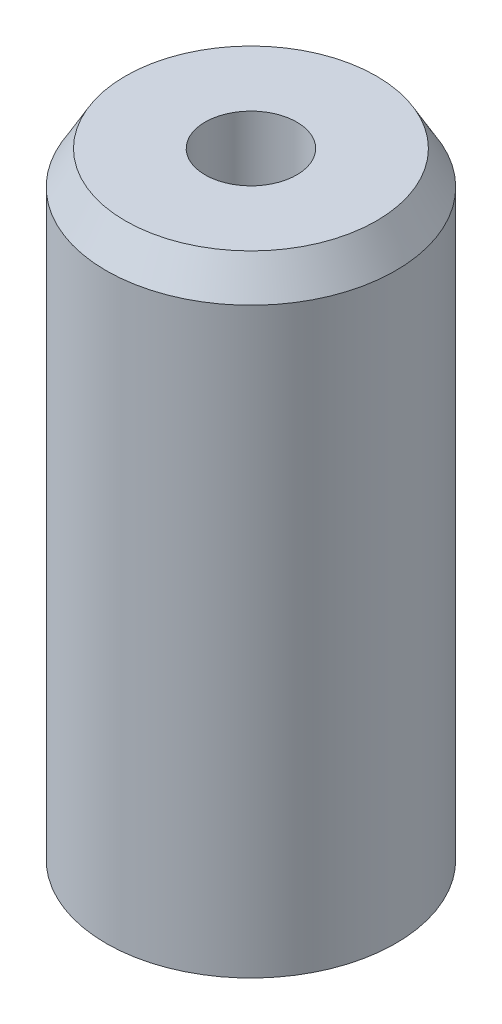
SolidWorks part; units mm, degrees
ref_plane "Front Plane" through (0, 0, 0) normal (0, 0, 1) x (1, 0, 0)
ref_plane "Top Plane" through (0, 0, 0) normal (0, 1, 0) x (1, 0, 0)
ref_plane "Right Plane" through (0, 0, 0) normal (1, 0, 0) x (0, 0, -1)
sketch "Sketch1" plane through (0, 0, 0) normal (0, 1, 0) x (1, 0, 0)
  circle A0 centre (0, 0) radius 20
  dimension "SHAFT_OD" = 40
extrude "Boss-Extrude1" add sketch "Sketch1" along normal blind 87.7578
sketch "Sketch2" plane through (0, 0, 0) normal (0, 1, 0) x (1, 0, 0)
  circle A0 centre (0, 0) radius 6.329
  dimension "BORE_D" = 12.658
extrude "Cut-Extrude1" cut sketch "Sketch2" along normal through all
chamfer "Chamfer1" distance 4.6152 angle 30 2 edges at (0, 87.7578, 20) (0, 0, 20) first distance on face at (0, 87.7578, 20) first distance on face at (0, 0, 6.329)
